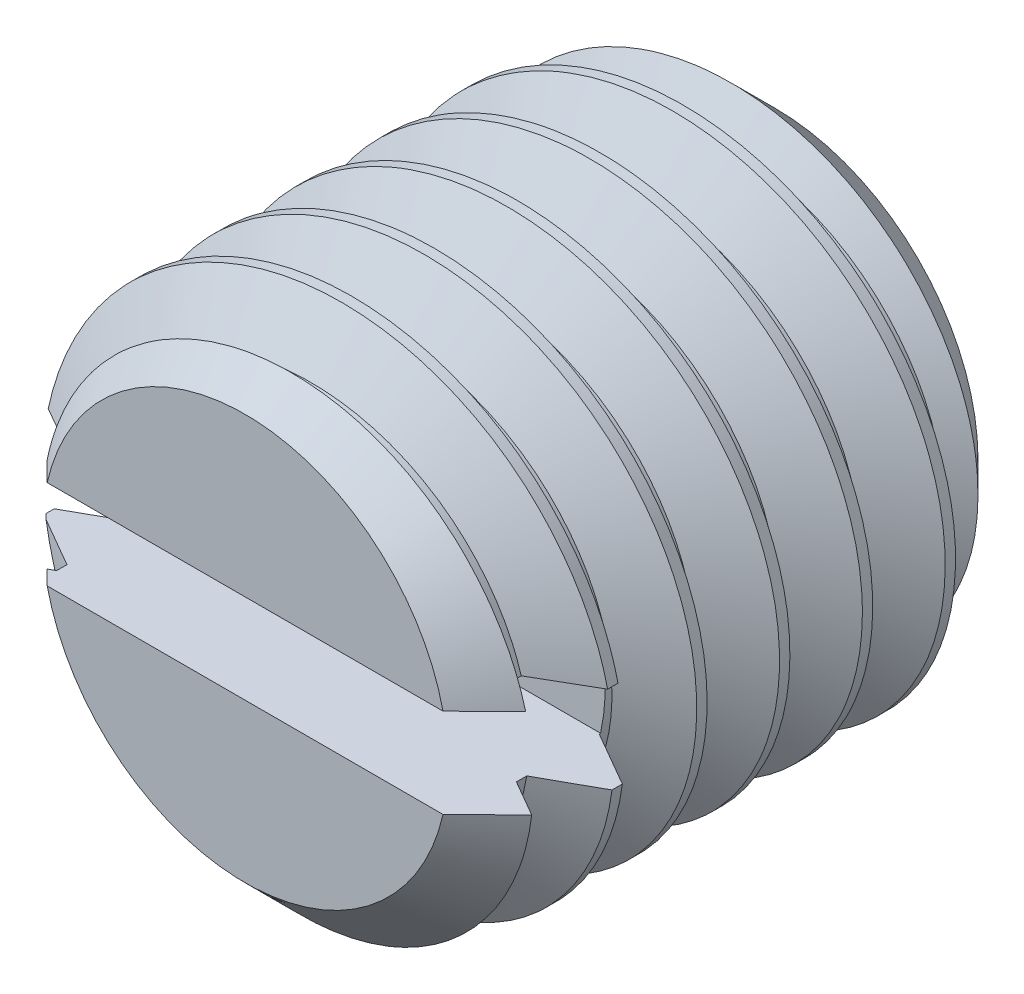
SolidWorks part; units mm, degrees
ref_plane "Front" through (0, 0, 0) normal (0, 0, 1) x (1, 0, 0)
ref_plane "Top" through (0, 0, 0) normal (0, 1, 0) x (1, 0, 0)
ref_plane "Right" through (0, 0, 0) normal (1, 0, 0) x (0, 0, -1)
sketch "Sketch1" plane through (0, 0, 0) normal (1, 0, 0) x (0, 0, -1)
  line L1 (4, 0) -> (-4, 0) construction
  line L3 (-4, 0) -> (-4, 3.0625) construction
  line L6 (-4, 3.0625) -> (-3.0625, 4) construction
  line L8 (-5.1719, 4.1353) -> (-3.9219, 4.1353) construction
  line L10 (-3.9219, 4.1353) -> (-4.5469, 3.0528) construction
  line L11 (-4.5469, 3.0528) -> (-5.1719, 4.1353) construction
  line L12 (-4.5469, 3.0528) -> (-4.5469, 3.1881) construction
  line L13 (-4.625, 3.1881) -> (-4.4687, 3.1881) construction
  line L14 (-5.0937, 4) -> (-4, 4) construction
  line L15 (-4.5469, 4.1353) -> (-4.5469, 4) construction
  line L16 (-5.1328, 4.0677) -> (-3.9609, 4.0677) construction
  line L17 (-3.0625, 4) -> (3.0625, 4) construction
  line L18 (3.0625, 4) -> (4, 3.0625) construction
  line L19 (4, 3.0625) -> (4, 0) construction
  line L21 (-1.75, -0.675) -> (-4, -0.675)
  line L22 (-1.75, -0.675) -> (-1.75, 0.675)
  line L23 (-1.75, 0.675) -> (-4, 0.675)
  line L24 (-4, -0.675) -> (-4, 0.675)
  line L25 (-2.875, 0.675) -> (-2.875, -0.675) construction
  line L26 (-1.75, 0) -> (-4, 0) construction
  point P0 (-2.875, 0)
  point P3 (0, 0)
  point P22 (-4.5469, 3.1881)
  point P25 (-4.5469, 4)
  point P28 (-4.5469, 4.0677)
  point P32 (0.375, 4)
  point P36 (0.375, -4)
  dimension "Thread Pitch" = 1.25
  dimension "D5" = 0.1562
  dimension "Length" = 8
  dimension "D1" = 45
  dimension "Thread Size" = 8
  dimension "D2" = 0.9375
  dimension "Slot Height" = 1.35
  dimension "Slot Depth" = 2.25
  dimension "D3" = 4.375
sketch "Sketch2" plane through (0, 0, 0) normal (1, 0, 0) x (0, 0, -1)
  line L0 (-4, 0) -> (-4, 3.0625)
  line L1 (-4, 3.0625) -> (-3.0625, 4)
  line L2 (-3.0625, 4) -> (3.0625, 4)
  line L3 (3.0625, 4) -> (4, 3.0625)
  line L4 (4, 3.0625) -> (4, 0)
  line L5 (4, 0) -> (-4, 0)
revolve "Revolve1" add sketch "Sketch2" angle 360 about L5
sketch "Sketch3" plane through (0, 0, 0) normal (1, 0, 0) x (0, 0, -1)
  line L1 (-4, 0.675) -> (-1.75, 0.675)
  line L2 (-4, 0.675) -> (-4, -0.675)
  line L3 (-4, -0.675) -> (-1.75, -0.675)
  line L4 (-1.75, 0.675) -> (-1.75, -0.675)
extrude "Cut-Extrude1" cut sketch "Sketch3" against normal through all both and the other way through all
sketch "Sketch4" plane through (0, 0, 4) normal (0, 0, 1) x (1, 0, 0)
  line L0 (0, 0.675) -> (0, -0.675) construction
  circle A0 centre (0, 0) radius 4
curve "Helix/Spiral1" pitch 1.25 height 9.25 radius 4 centre (0, 0, 4) axis (0, 0, -1) start towards (0, 1, 0)
sketch "Sketch5" plane through (0, 0, 0) normal (1, 0, 0) x (0, 0, -1)
  line L0 (-5.1328, 4.0677) -> (-3.9609, 4.0677)
  line L1 (-3.9609, 4.0677) -> (-4.4687, 3.1881)
  line L2 (-3.9219, 4.1353) -> (-4.5469, 3.0528) construction
  line L3 (-4.4687, 3.1881) -> (-4.625, 3.1881)
  line L4 (-4.625, 3.1881) -> (-5.1328, 4.0677)
sweep "Cut-Sweep1" cut profiles "Sketch5" path "Helix/Spiral1"
equation "\"D2@Sketch1\"=\"Thread Pitch@Sketch1\"*.75"
equation "\"D3@Helix/Spiral1\"=\"Length@Sketch1\"+\"D4@Helix/Spiral1\""
equation "\"D4@Helix/Spiral1\"=\"Thread Pitch@Sketch1\""
equation "\"D5@Sketch1\"=\"Thread Pitch@Sketch1\"/8"
equation "\"D3@Sketch1\"=\"Thread Pitch@Sketch1\"*3.5"
